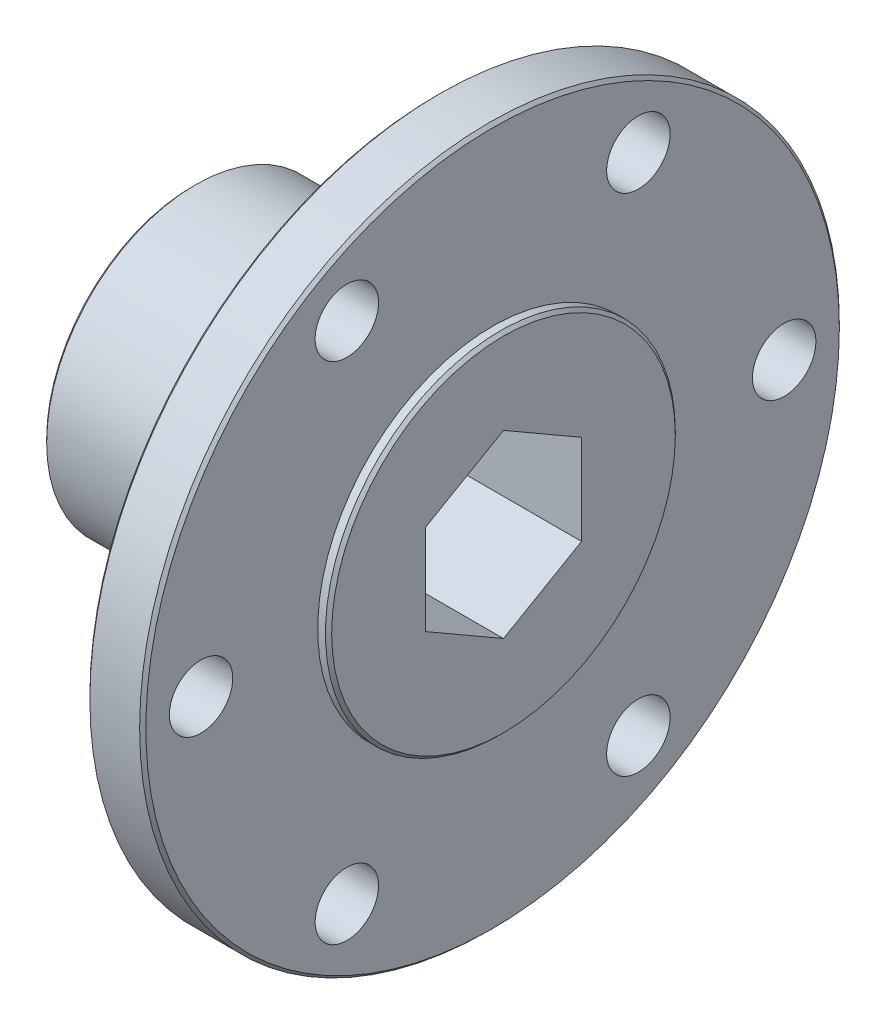
SolidWorks part; units mm, degrees
ref_plane "Front Plane" through (0, 0, 0) normal (0, 0, 1) x (1, 0, 0)
ref_plane "Top Plane" through (0, 0, 0) normal (0, 1, 0) x (1, 0, 0)
ref_plane "Right Plane" through (0, 0, 0) normal (1, 0, 0) x (0, 0, -1)
ref_axis "Axis1" through (0, 0, 0) along (1, 0, 0)
sketch "Sketch1" plane through (0, 0, 0) normal (0, 0, 1) x (1, 0, 0)
  line L0 (-6.0149, 12.1666) -> (-6.0149, 0)
  line L1 (-6.0149, 0) -> (19.3851, 0)
  line L2 (19.3851, 0) -> (19.3851, 14.2875)
  line L3 (19.3851, 14.2875) -> (18.4961, 14.2875)
  line L4 (18.4961, 14.2875) -> (18.4961, 28.575)
  line L5 (18.4961, 28.575) -> (13.9241, 28.575)
  line L6 (13.9241, 28.575) -> (13.9241, 14.2875)
  line L7 (13.9241, 14.2875) -> (13.0351, 14.2875)
  line L8 (13.0351, 14.2875) -> (13.0351, 12.9794)
  line L9 (13.0351, 12.9794) -> (12.2223, 12.1666)
  line L10 (12.2223, 12.1666) -> (-6.0149, 12.1666)
  line L11 (-6.0149, 0) -> (19.3851, 0) construction
revolve "Revolve1" add sketch "Sketch1" angle 360 about L11 reverse direction yes
sketch "Sketch2" plane through (18.4961, 0, 0) normal (1, 0, 0) x (0, 0, -1)
  circle A0 centre (-11.9063, -20.6222) radius 2.5908
extrude "Cut-Extrude1" cut sketch "Sketch2" against normal through all
pattern_circular "CirPattern1" count 6 over 360 about axis through (0, 0, 0) along (1, 0, 0) of "Cut-Extrude1"
sketch "Sketch3" plane through (19.3851, 0, 0) normal (1, 0, 0) x (0, 0, -1)
  line L0 (0, 7.3617) -> (-6.3754, 3.6808)
  line L1 (-6.3754, 3.6808) -> (-6.3754, -3.6809)
  line L2 (-6.3754, -3.6809) -> (0, -7.3617)
  line L3 (0, -7.3617) -> (6.3754, -3.6809)
  line L4 (6.3754, -3.6809) -> (6.3754, 3.6808)
  line L5 (6.3754, 3.6808) -> (0, 7.3617)
extrude "Cut-Extrude2" cut sketch "Sketch3" against normal through all
chamfer "Chamfer1" distance 0.254 angle 45 5 edges at (19.3851, 0, -14.2875) (-6.0149, 0, -12.1666) (18.4961, 0, -28.575) (13.0351, 0, -14.2875) (13.9241, 0, -28.575)
